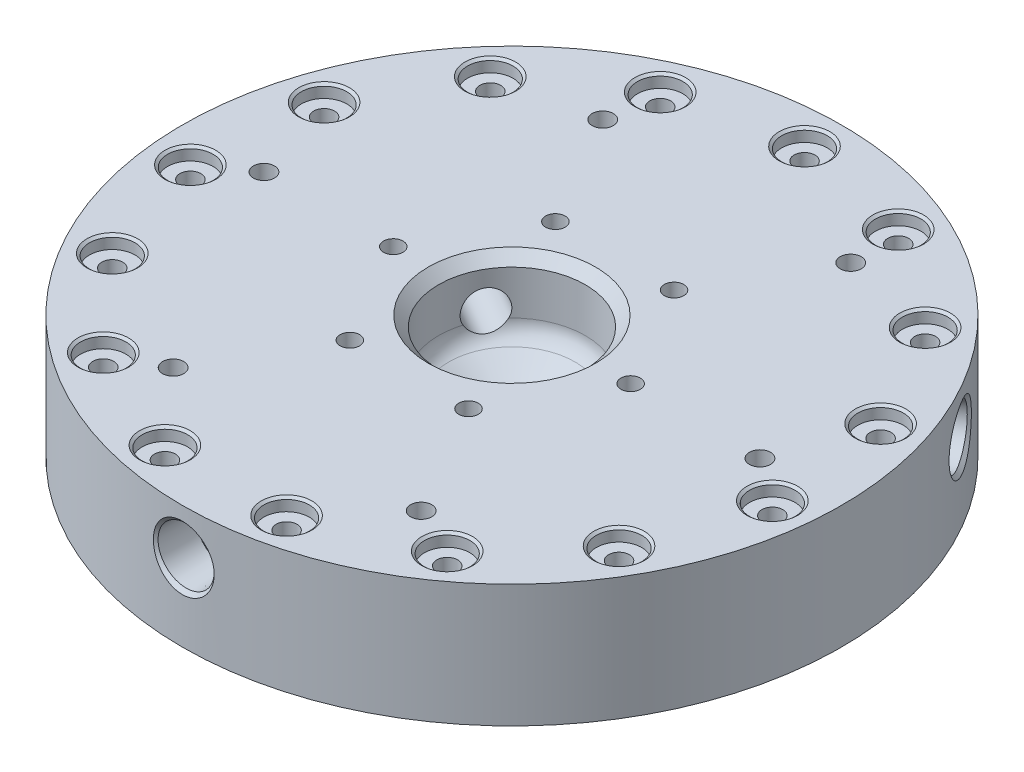
SolidWorks part; units mm, degrees
ref_plane "Front Plane" through (0, 0, 0) normal (0, 0, 1) x (1, 0, 0)
ref_plane "Top Plane" through (0, 0, 0) normal (0, 1, 0) x (1, 0, 0)
ref_plane "Right Plane" through (0, 0, 0) normal (1, 0, 0) x (0, 0, -1)
sketch "Sketch1" plane through (0, 0, 0) normal (0, 1, 0) x (1, 0, 0)
  circle A0 centre (0, 0) radius 80.54
  dimension "D1" = 161.08
extrude "Boss-Extrude1" add sketch "Sketch1" along normal blind 30
sketch "Sketch2" plane through (0, 0, 0) normal (0, 0, 1) x (1, 0, 0)
  line L0 (-6.0682, 0) -> (-6.0682, 4.1132)
  line L1 (-8.5682, 8.4434) -> (-15.4203, 12.3995)
  line L2 (-17.9203, 16.7296) -> (-17.9203, 30)
  line L3 (80.54, 30) -> (-80.54, 30) construction
  line L4 (-17.9203, 30) -> (0, 30)
  line L5 (0, 30) -> (0, 0)
  line L6 (0, 0) -> (-6.0682, 0)
  line L7 (-80.54, 0) -> (80.54, 0) construction
  arc A0 (-15.4203, 12.3995) -> (-17.9203, 16.7296) centre (-12.9203, 16.7296) cw
  arc A1 (-6.0682, 4.1132) -> (-8.5682, 8.4434) centre (-11.0682, 4.1132) ccw
  point P15 (-6.0682, 7)
  dimension "D5" = 5
  dimension "Fuel Outlet Radius" = 6.0682
  dimension "D2" = 7
  dimension "Fuel Chamber Radius" = 17.9203
  dimension "D4" = 30
revolve "Cut-Revolve1" cut sketch "Sketch2" angle 360 about L5
ref_plane "Plane1" through (0, 0, 80.54) normal (0, 0, 1) x (1, 0, 0)
hole_wizard "1/4 NPT Tapped Hole1" positions "Sketch4" profile "Sketch5" size "1/4" standard "ANSI Inch"
sketch "Sketch4" plane through (0, 0, 80.54) normal (0, 0, 1) x (1, 0, 0)
  point P0 (0, 18.9048)
sketch "Sketch5" plane through (0, 18.9048, 80.54) normal (1, 0, 0) x (0, -1, 0)
  line L0 (0, 0) -> (0, 83.3213)
  line L1 (4.6289, 80.54) -> (0, 83.3213)
  line L2 (-4.6289, 80.54) -> (0, 83.3213) construction
  line L3 (4.6289, 80.54) -> (4.6289, 10.02)
  line L4 (4.6289, 10.02) -> (6.5855, 10.02)
  line L5 (6.5855, 10.02) -> (6.858, 0.9208)
  line L6 (6.858, 0.9208) -> (7.7788, 0)
  line L7 (7.7788, 0) -> (0, 0)
  line L8 (0, -6.35) -> (0, 107.95) construction
  line L9 (-6.858, 0.9208) -> (-7.7788, 0) construction
  line L11 (-4.6289, 10.02) -> (-6.5855, 10.02) construction
  line L12 (-6.5855, 10.02) -> (-6.858, 0.9208) construction
  dimension "Fuel Inlet Diameter" = 9.2579
  dimension "Tap Drill Depth" = 80.54
  dimension "Thread Dia." = 13.716
  dimension "Thread Angle" = 3.43
  dimension "Thread Depth" = 10.02
  dimension "C'Sink Dia." = 15.5575
  dimension "C'Sink Angle" = 90
  dimension "Drill Angle" = 118
pattern_circular "CirPattern1" count 3 over 360 about axis through (0, 30, 0) along (0, -1, 0) of "1/4 NPT Tapped Hole1"
hole_wizard "CBORE for #10 Binding Head Machine Screw1" positions "Sketch6" profile "Sketch7" counterbore size "#10" standard "ANSI Inch" end condition through all
sketch "Sketch6" plane through (0, 30, 0) normal (0, 1, 0) x (1, 0, 0)
  point P0 (0, 71.5)
  dimension "D1" = 71.5
sketch "Sketch7" plane through (0, 30, -71.5) normal (1, 0, 0) x (0, 0, 1)
  line L0 (0, 0) -> (0, 30)
  line L1 (0, 30) -> (2.5527, 30)
  line L3 (2.5527, 30) -> (2.5527, 3.1242)
  line L4 (5.5562, 3.1242) -> (2.5527, 3.1242)
  line L5 (5.5562, 3.1242) -> (5.5562, 0.5328)
  line L6 (5.5562, 0.5328) -> (6.1913, 0)
  line L7 (6.1913, 0) -> (0, 0)
  line L8 (-5.5562, 0.5328) -> (-6.1913, 0) construction
  line L11 (0, -6.35) -> (0, 107.95) construction
  dimension "Thru Hole Dia." = 5.1054
  dimension "Thru Hole Depth" = 30
  dimension "C'Bore Dia." = 11.1125
  dimension "C'Bore Depth" = 3.1242
  dimension "Near C'Sink Dia." = 12.3825
  dimension "Near C'Sink Angle" = 100
pattern_circular "CirPattern2" count 15 over 360 about axis through (0, 30, 0) along (0, -1, 0) of "CBORE for #10 Binding Head Machine Screw1"
sketch "Sketch12" plane through (0, 30, 0) normal (0, 1, 0) x (1, 0, 0)
  line L0 (0, 0) -> (0, 60.61)
  line L1 (0, 0) -> (30.305, 52.4898)
  circle A0 centre (0, 0) radius 60.61
  dimension "D1" = 121.22
  dimension "D2" = 30
hole_wizard "13/64 (0.20313) Diameter Hole3" positions "Sketch17" profile "Sketch19" hole size "13/64" standard "ANSI Inch"
sketch "Sketch17" plane through (0, 30, 0) normal (0, 1, 0) x (1, 0, 0)
  point P0 (30.305, 52.4898)
sketch "Sketch19" plane through (30.305, 30, -52.4898) normal (1, 0, 0) x (0, 0, 1)
  line L0 (0, 0) -> (0, 14.2501)
  line L1 (0, 14.2501) -> (2.5798, 12.7)
  line L2 (2.5798, 12.7) -> (2.5798, 0)
  line L5 (2.5798, 0) -> (0, 0)
  line L10 (0, 14.2501) -> (-2.5798, 12.7) construction
  line L11 (0, -6.35) -> (0, 107.95) construction
  dimension "Hole Dia." = 5.1595
  dimension "Hole Depth" = 12.7
  dimension "Drill Angle" = 118
pattern_circular "CirPattern3" count 6 over 360 about axis through (0, 30, 0) along (0, -1, 0) of "13/64 (0.20313) Diameter Hole3" reverse direction yes
sketch "Sketch20" plane through (0, 0, 0) normal (0, -1, 0) x (-1, 0, 0)
  circle A0 centre (0, 0) radius 55.14
  dimension "D1" = 110.28
sketch "Sketch21" plane through (0, 0, 0) normal (0, 0, 1) x (1, 0, 0)
  line L0 (-80.54, 0) -> (80.54, 0) construction
  line L1 (60, 0) -> (65, 0)
  line L2 (60, 0) -> (60, 3)
  line L3 (60, 3) -> (65, 3)
  line L4 (65, 0) -> (65, 3)
  line L5 (0, 0) -> (0, -8.9782) construction
  dimension "D1" = 60
  dimension "D2" = 5
  dimension "D3" = 3
revolve "Cut-Revolve2" cut sketch "Sketch21" angle 360 about L5
chamfer "Chamfer1" distance 2.5 angle 45 1 edges at (-17.9203, 30, 0)
hole_wizard "3/16 (0.1875) Diameter Hole1" positions "Sketch27" profile "Sketch28" hole size "3/16" standard "ANSI Inch"
sketch "Sketch27" plane through (0, 30, 0) normal (0, 1, 0) x (1, 0, 0)
  point P0 (29, 0)
  dimension "D1" = 29
sketch "Sketch28" plane through (29, 30, 0) normal (1, 0, 0) x (0, 0, 1)
  line L0 (0, 0) -> (0, 13.4308)
  line L1 (0, 13.4308) -> (2.3812, 12)
  line L2 (2.3812, 12) -> (2.3812, 0)
  line L5 (2.3812, 0) -> (0, 0)
  line L10 (0, 13.4308) -> (-2.3813, 12) construction
  line L11 (0, -6.35) -> (0, 107.95) construction
  dimension "Hole Dia." = 4.7625
  dimension "Hole Depth" = 12
  dimension "Drill Angle" = 118
pattern_circular "CirPattern4" count 6 over 360 about axis through (0, 30, 0) along (0, -1, 0) of "3/16 (0.1875) Diameter Hole1" reverse direction yes
